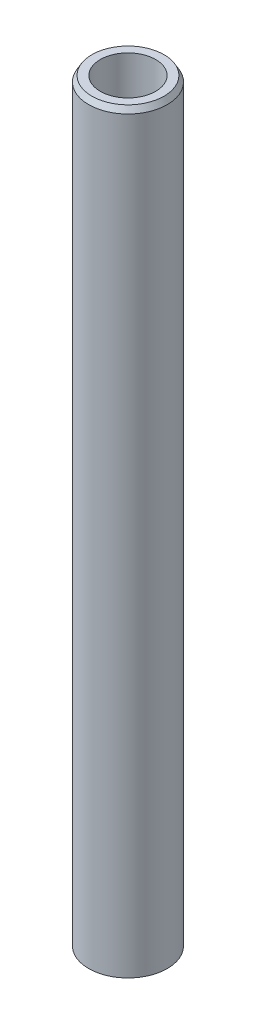
SolidWorks part; units mm, degrees
ref_plane "Front Plane" through (0, 0, 0) normal (0, 0, 1) x (1, 0, 0)
ref_plane "Top Plane" through (0, 0, 0) normal (0, 1, 0) x (1, 0, 0)
ref_plane "Right Plane" through (0, 0, 0) normal (1, 0, 0) x (0, 0, -1)
sketch "Sketch1" plane through (0, 0, 0) normal (0, 1, 0) x (1, 0, 0)
  circle A0 centre (0, 0) radius 15
  dimension "SHAFT_OD" = 30
extrude "Boss-Extrude1" add sketch "Sketch1" along normal blind 288.9765
sketch "Sketch2" plane through (0, 0, 0) normal (0, 1, 0) x (1, 0, 0)
  circle A0 centre (0, 0) radius 10.556
  dimension "BORE_D" = 21.112
extrude "Cut-Extrude1" cut sketch "Sketch2" along normal through all
chamfer "Chamfer1" distance 2.1615 angle 30 2 edges at (0, 288.9765, 15) (0, 0, 15) first distance on face at (0, 288.9765, 15) first distance on face at (0, 0, 10.556)
